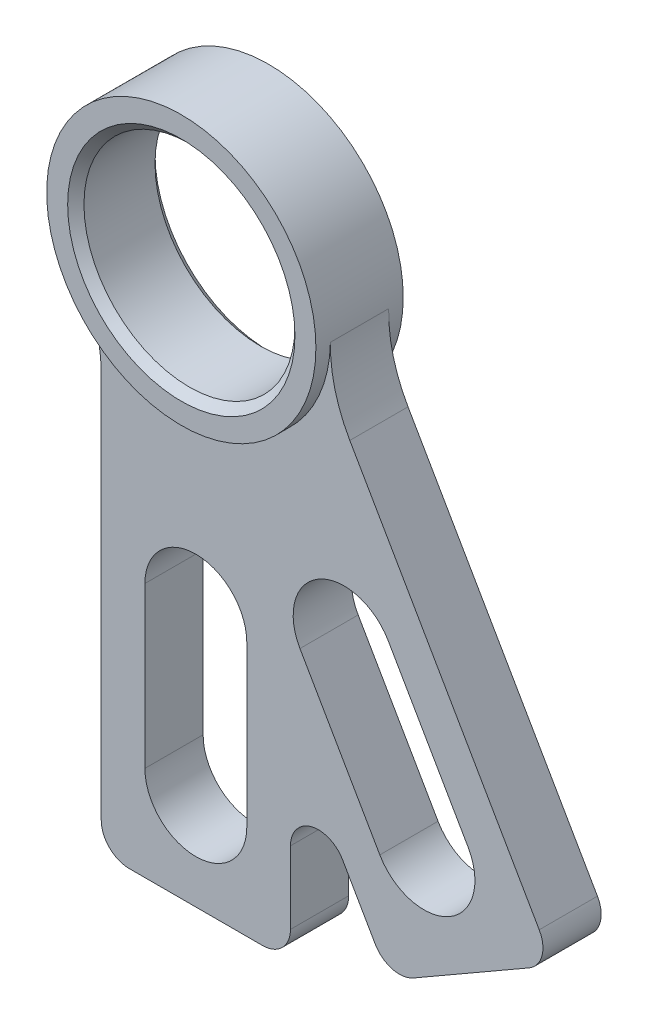
SolidWorks part; units mm, degrees
material "AISI 4130 Steel, annealed at 865C"
ref_plane "X-Y Datum" through (0, 0, 0) normal (0, 0, 1) x (1, 0, 0)
ref_plane "X-Z Datum" through (0, 0, 0) normal (0, 1, 0) x (1, 0, 0)
ref_plane "Y-Z Datum" through (0, 0, 0) normal (1, 0, 0) x (0, 0, -1)
sketch "Sketch1" plane through (0, 0, 0) normal (0, 0, 1) x (1, 0, 0)
  line L0 (0, -50.6413) -> (0, -33.1787) construction
  line L1 (-5.5562, -50.6413) -> (-5.5562, -33.1787)
  line L2 (5.5562, -50.6413) -> (5.5562, -33.1787)
  line L4 (20.0653, -46.0005) -> (11.3543, -30.8658)
  line L5 (29.6964, -40.4572) -> (20.9855, -25.3225)
  line L6 (-10.3187, -15.7343) -> (-10.3187, -60.96)
  line L7 (-10.3187, -60.96) -> (10.3187, -60.96)
  line L10 (21.085, -57.3194) -> (38.9714, -47.0247)
  line L11 (38.9714, -47.0247) -> (16.7921, -8.4895)
  line L12 (0, 0) -> (0, -389.1111) construction
  line L13 (10.3187, -60.96) -> (10.3187, -38.6138)
  line L14 (0, -56.1975) -> (0, -60.96) construction
  line L15 (27.6525, -48.0444) -> (30.0282, -52.1721) construction
  line L16 (25.341, -32.8899) -> (29.4686, -30.5141) construction
  line L17 (-5.5562, -41.91) -> (-10.3187, -41.91) construction
  line L18 (-10.3187, -22.86) -> (10.3187, -22.86) construction
  line L19 (10.3187, -22.86) -> (10.3187, -60.96) construction
  line L20 (5.5562, -41.91) -> (10.3187, -41.91) construction
  line L21 (0, -27.6225) -> (0, -22.86) construction
  line L22 (21.085, -57.3194) -> (2.0793, -24.2983) construction
  line L23 (2.0793, -24.2983) -> (19.9658, -14.0036) construction
  line L24 (15.7098, -38.4332) -> (11.5822, -40.8089) construction
  line L25 (13.3983, -23.2786) -> (11.0225, -19.151) construction
  line L29 (21.085, -57.3194) -> (10.3187, -38.6138)
  line L30 (0, 0) -> (194.1029, -337.241) construction
  line L32 (0, -364.1414) -> (0, 0) construction
  line L33 (0, -389.1111) -> (194.1029, -337.241) construction
  line L34 (97.0514, -363.1761) -> (0, 0) construction
  circle A0 centre (0, 0) radius 11.5062
  arc A1 (-5.5562, -50.6413) -> (5.5562, -50.6413) centre (0, -50.6413) ccw
  arc A2 (5.5562, -33.1787) -> (-5.5562, -33.1787) centre (0, -33.1787) ccw
  arc A3 (20.0653, -46.0005) -> (29.6964, -40.4572) centre (24.8809, -43.2289) ccw
  arc A4 (20.9855, -25.3225) -> (11.3543, -30.8658) centre (16.1699, -28.0942) ccw
  arc A5 (14.6786, -0.2741) -> (-12.5852, -7.5598) centre (0, 0) ccw
  arc A6 (16.7921, -8.4895) -> (14.6786, -0.2741) centre (30.5509, -0.5705) cw
  arc A7 (-10.3187, -15.7343) -> (-12.5852, -7.5598) centre (-26.1937, -15.7343) ccw
  arc A14 (-12.5852, -7.5598) -> (14.6786, -0.2741) centre (0, 0) ccw
  point P5 (0, -41.91)
  point P11 (24.7297, -33.8362)
  point P31 (0, -60.96)
  point P39 (0, 0)
  point P52 (0, -389.7359)
  point P53 (0, 0)
  point P55 (29.8817, 2.7529)
  point P58 (0, 0)
  point P59 (0, 0)
  dimension "D1" = 23.0124
  dimension "D2" = 3.175
  dimension "D9" = 200.914
  dimension "D3" = 5.5562
  dimension "D4" = 11.1125
  dimension "D10" = 375.92
extrude "Boss-Extrude2" add sketch "Sketch1" along normal mid plane 9.525 contours A5 A14 A0 region at (-3.683, 13.7823, 0)
extrude "Boss-Extrude3" add sketch "Sketch1<4>" along normal mid plane 6.35 contours A14 A7 L6 L7 L10 L11 A6 A4 L5 A3 L4 A2 L2 A1 L1 region at (8.9818, -34.2249, 0)
sketch "Sketch1<4>" plane through (0, 0, 0) normal (0, 0, 1) x (1, 0, 0) same geometry as "Sketch1"
fillet "Fillet1" radius 3.048 5 edges at (-10.3187, -60.96, 0) (38.9714, -47.0247, 0) (10.3187, -38.6138, 0) (10.3187, -60.96, 0) (21.085, -57.3194, 0)
chamfer "Chamfer1" distance 0.889 angle 45 2 edges at (11.5062, 0, -4.7625) (11.5062, 0, 4.7625)
sketch "Sketch2" plane through (0, 0, 3.175) normal (0, 0, 1) x (1, 0, 0)
  line L0 (12.5798, -47.075) -> (0, 0) construction
  line L1 (0, 0) -> (-3.7903, 14.1835) construction
  line L2 (0, 0) -> (-11.1161, -2.9706) construction
  arc A0 (16.0084, -48.4992) -> (10.3187, -50.0197) centre (13.3667, -50.0197) ccw construction
  circle A1 centre (0, 0) radius 14.6812 construction
  circle A2 centre (0, 0) radius 11.5062 construction
ref_plane "Plane1" through (0, 0, 0) normal (-0.2582, 0.9661, 0) x (0, 0, 1)
